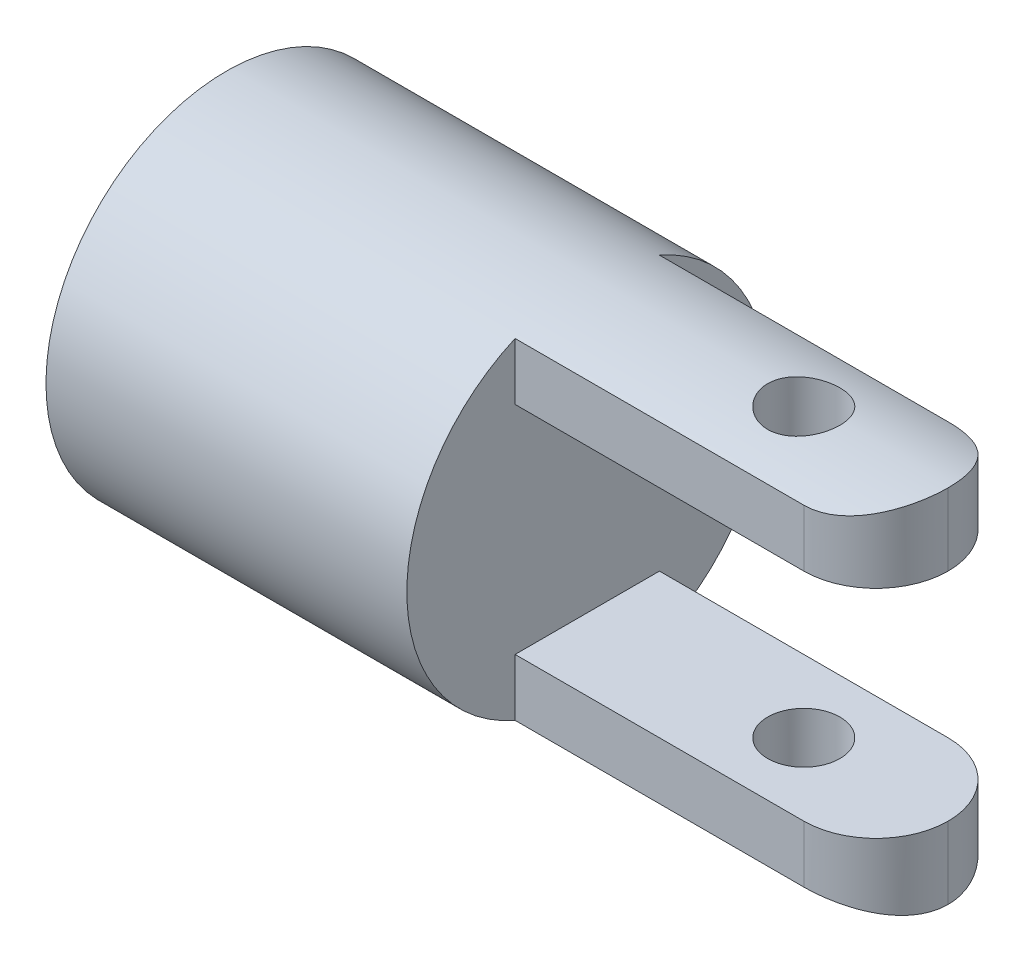
SolidWorks part; units mm, degrees
ref_plane "Ebene vorne" through (0, 0, 0) normal (0, 0, 1) x (1, 0, 0)
ref_plane "Ebene oben" through (0, 0, 0) normal (0, 1, 0) x (1, 0, 0)
ref_plane "Ebene rechts" through (0, 0, 0) normal (1, 0, 0) x (0, 0, -1)
sketch "Skizze7" plane through (0, 0, 0) normal (1, 0, 0) x (0, 0, -1)
  circle A0 centre (0, 0) radius 5
  dimension "D1" = 10
extrude "Aufsatz-Linear austragen4" add sketch "Skizze7" along normal mid plane 20
sketch "Skizze8" plane through (0, 0, 0) normal (0, 0, 1) x (1, 0, 0)
  line L0 (10, -5) -> (10, 5) construction
  line L1 (0, 3) -> (10, 3)
  line L2 (0, 3) -> (0, -3)
  line L3 (0, -3) -> (10, -3)
  line L4 (10, 3) -> (10, -3)
  dimension "D1" = 6
extrude "Schnitt-Linear austragen2" cut sketch "Skizze8" against normal through all and the other way through all
sketch "Skizze5" plane through (0, 0, 0) normal (0, 1, 0) x (1, 0, 0)
  line L0 (6, 0) -> (10, 0) construction
  line L2 (10, -4) -> (10, 4) construction
  line L4 (0, 5) -> (10, 5)
  line L5 (0, 5) -> (0, 2)
  line L6 (0, 2) -> (10, 2)
  line L7 (10, 5) -> (10, 2)
  line L8 (10, -2) -> (0, -2)
  line L9 (10, -2) -> (10, -5)
  line L10 (10, -5) -> (0, -5)
  line L11 (0, -2) -> (0, -5)
  circle A0 centre (6, 0) radius 1
  dimension "D1" = 2
  dimension "D2" = 4
  dimension "D3" = 3
  dimension "D4" = 3
extrude "Schnitt-Linear austragen3" cut sketch "Skizze5" against normal through all and the other way through all
ref_axis "Achse1" through (10, 0, 0) along (-1, 0, 0)
fillet "Verrundung1" radius 2 4 edges at (10, -3.7913, -2) (10, -3.7913, 2) (10, 3.7913, -2) (10, 3.7913, 2)
